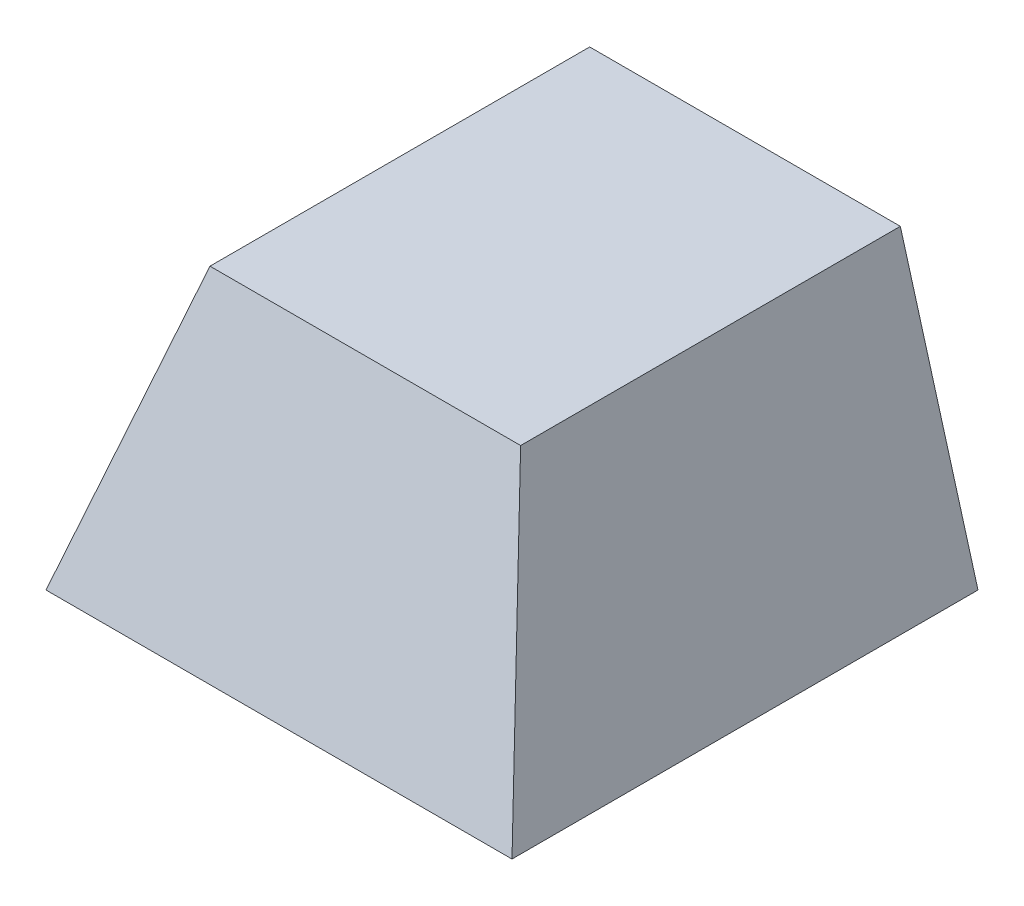
SolidWorks part; units mm, degrees
ref_plane "Front Plane" through (0, 0, 0) normal (0, 0, 1) x (1, 0, 0)
ref_plane "Top Plane" through (0, 0, 0) normal (0, 1, 0) x (1, 0, 0)
ref_plane "Right Plane" through (0, 0, 0) normal (1, 0, 0) x (0, 0, -1)
sketch "Sketch1" plane through (0, 0, 0) normal (0, 0, 1) x (1, 0, 0)
  line L0 (-124.4923, -61.6423) -> (-79.4923, 98.3577)
  line L5 (-124.4923, -61.6423) -> (145.5077, -61.6423)
  line L9 (10.5077, 98.3577) -> (10.5077, -61.6423) construction
  line L10 (-79.4923, 98.3577) -> (100.5077, 98.3577)
  line L11 (145.5077, -61.6423) -> (100.5077, 98.3577)
  dimension "D1" = 270
  dimension "D2" = 160
  dimension "D3" = 90
extrude "Boss-Extrude1" add sketch "Sketch1" along normal blind 270
sketch "Sketch3" plane through (-99.3006, 27.9283, 0) normal (-0.9627, 0.2707, 0) x (0, 0, 1)
  line L0 (135, 73.1619) -> (135, -93.0458) construction
  line L1 (270, 73.1619) -> (0, 73.1619) construction
  line L2 (270, -93.0458) -> (0, -93.0458) construction
  line L3 (0, 73.1619) -> (220, 73.1619)
  line L8 (220, 73.1619) -> (270, 73.1619)
  line L9 (270, 73.1619) -> (270, -93.0458)
  line L10 (220, 73.1619) -> (270, -93.0458)
  point P12 (182.682, 73.1619)
  line M6 (270, -93.0458) -> (270, 73.1619)
  line M7 (270, 73.1619) -> (0, 73.1619)
  dimension "D1" = 220
extrude "Cut-Extrude2" cut sketch "Sketch3" along direction (-1, 0, 0) on the side against the normal blind 280 contours L10 M7 M6 region at (-94.4923, 45.0243, 253.3333)
